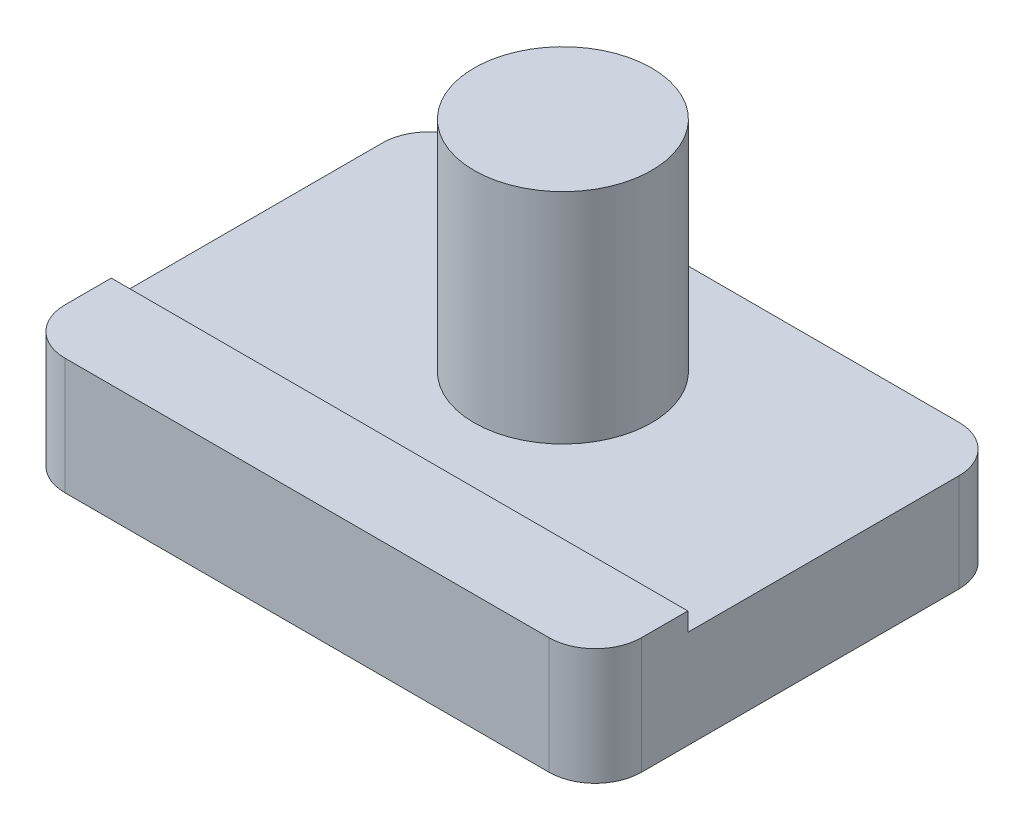
SolidWorks part; units mm, degrees
ref_plane "前视基准面" through (0, 0, 0) normal (0, 0, 1) x (1, 0, 0)
ref_plane "上视基准面" through (0, 0, 0) normal (0, 1, 0) x (1, 0, 0)
ref_plane "右视基准面" through (0, 0, 0) normal (1, 0, 0) x (0, 0, -1)
other "Configuration Table"
sketch "草图1" plane through (0, 0, 0) normal (0, 1, 0) x (1, 0, 0)
  line L0 (-31.15, -12.15) -> (31.15, -12.15)
  line L1 (-31.15, 22.15) -> (31.15, 22.15)
  line L2 (-31.15, 22.15) -> (-31.15, -22.15)
  line L3 (-31.15, -22.15) -> (31.15, -22.15)
  line L4 (31.15, 22.15) -> (31.15, -22.15)
  line L5 (-31.15, 22.15) -> (31.15, -22.15) construction
  line L6 (-31.15, -22.15) -> (31.15, 22.15) construction
  point P0 (0, 0)
  dimension "D1" = 62.3
  dimension "D2" = 44.3
  dimension "D3" = 10
extrude "凸台-拉伸1" add sketch "草图1" along normal blind 10.6 contours L4 L1 L2 L0 region at (0, 0, -5)
extrude "凸台-拉伸2" add sketch "草图1<3>" along normal blind 12.6 contours L4 L0 L2 L3 region at (0, 0, 17.15)
sketch "草图1<3>" plane through (0, 0, 0) normal (0, 1, 0) x (1, 0, 0) same geometry as "草图1"
sketch "草图4" plane through (0, 10.6, 0) normal (0, 1, 0) x (1, 0, 0)
  circle A0 centre (0, 5.5002) radius 9.5937
  point P2 (0, 9.749)
  point P3 (0, 6.4543)
  point P4 (0, 0)
  point P5 (0, 0)
  point P6 (-0.2967, 5.5002)
  point P7 (0, 5.5002)
extrude "凸台-拉伸3" add sketch "草图4" along normal blind 23.62
fillet "圆角1" radius 5 4 edges at (-31.15, 6.3, 22.15) (-31.15, 5.3, -22.15) (31.15, 6.3, 22.15) (31.15, 5.3, -22.15)
